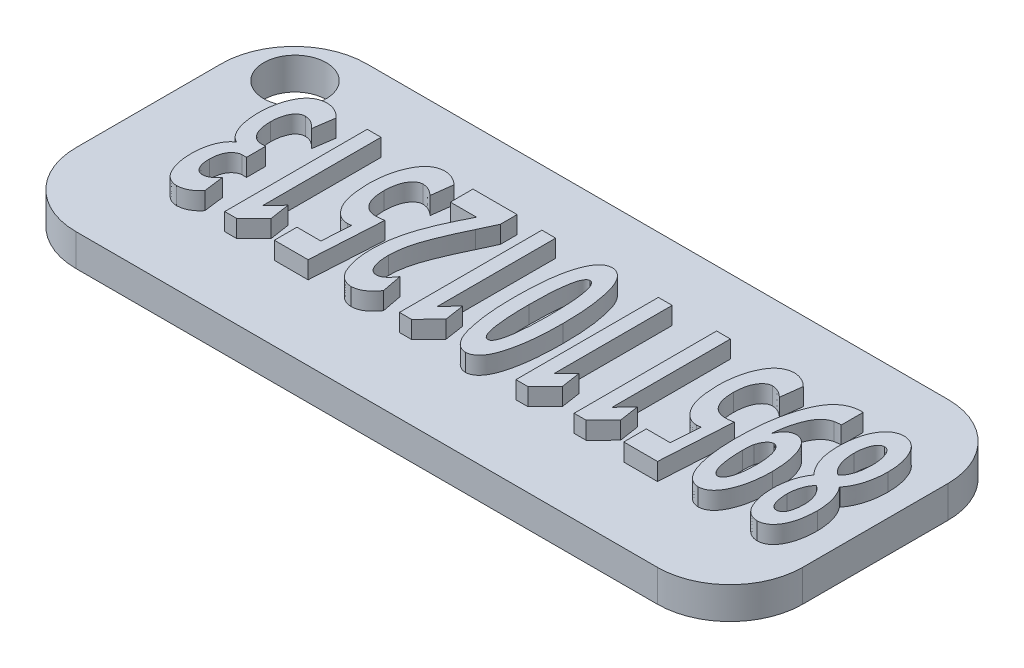
SolidWorks part; units mm, degrees
ref_plane "Спереди" through (0, 0, 0) normal (0, 0, 1) x (1, 0, 0)
ref_plane "Сверху" through (0, 0, 0) normal (0, 1, 0) x (1, 0, 0)
ref_plane "Справа" through (0, 0, 0) normal (1, 0, 0) x (0, 0, -1)
other "Configuration Table"
sketch "Эскиз1" plane through (0, 0, 0) normal (0, 1, 0) x (1, 0, 0)
  line L1 (0, 0) -> (50, 0)
  line L2 (0, 0) -> (0, 20)
  line L3 (0, 20) -> (50, 20)
  line L4 (50, 0) -> (50, 20)
  dimension "D1" = 20
  dimension "D2" = 50
extrude "Бобышка-Вытянуть1" add sketch "Эскиз1" along normal blind 2.2 contours L2 L3 L4 L1
fillet "Скругление1" radius 5 1 edges at (0, 1.1, -20)
fillet "Скругление2" radius 5 1 edges at (0, 1.1, 0)
fillet "Скругление3" radius 5 1 edges at (50, 1.1, -20)
fillet "Скругление4" radius 5 1 edges at (50, 1.1, 0)
sketch "Эскиз4" plane through (0, 2.2, 0) normal (0, 1, 0) x (1, 0, 0)
  circle A0 centre (3.5425, 16.5284) radius 2.1519
extrude "Вырез-Вытянуть1" cut sketch "Эскиз4" against normal blind 3
sketch "Эскиз5" plane through (0, 2.2, 0) normal (0, -1, 0) x (1, 0, 0)
  line L0 (0, -15) -> (50.4167, -15) construction
  arc A0 (0, -15) -> (5, -20) centre (5, -15) ccw construction
  text T0 "<b> 89511012513</b>" font "@Adobe Gothic Std B" height 10
extrude "надпись" add sketch "Эскиз5" along normal blind 1.2 and the other way blind 1.2
